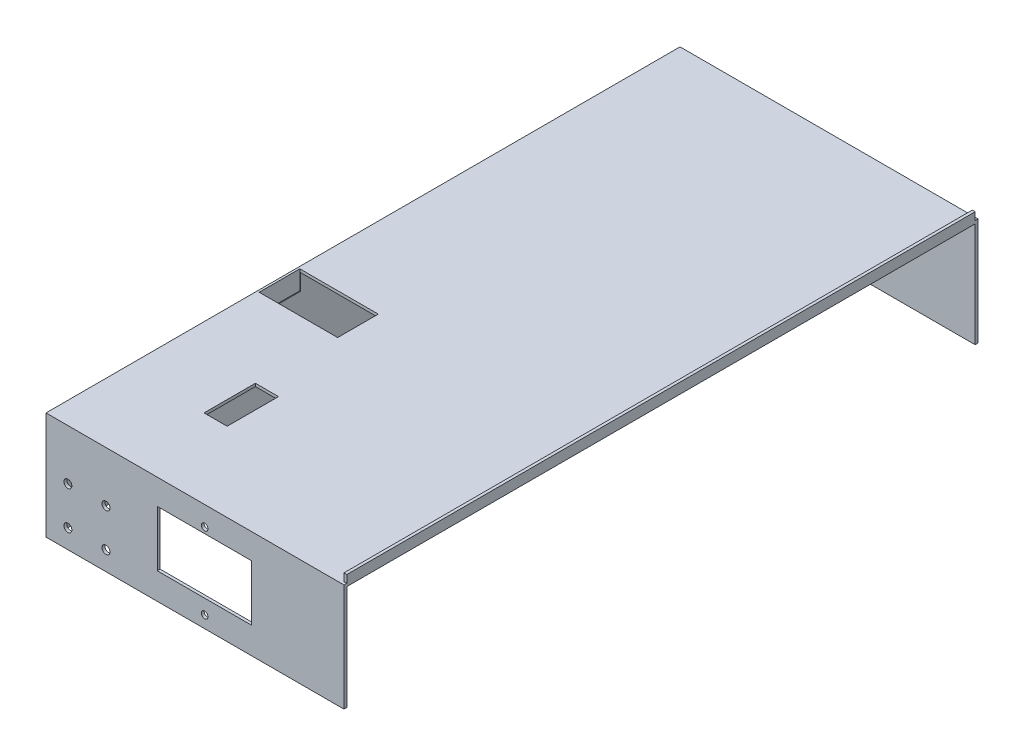
SolidWorks part; units mm, degrees
ref_plane "Front Plane" through (0, 0, 0) normal (0, 0, 1) x (1, 0, 0)
ref_plane "Top Plane" through (0, 0, 0) normal (0, 1, 0) x (1, 0, 0)
ref_plane "Right Plane" through (0, 0, 0) normal (1, 0, 0) x (0, 0, -1)
sketch "Sketch4" plane through (0, 0, 0) normal (0, 1, 0) x (1, 0, 0)
  line L0 (189.3737, 330) -> (344.3737, 330)
  line L1 (344.3737, 330) -> (344.3737, 0)
  line L2 (344.3737, 0) -> (189.3737, 0)
  line L3 (189.3737, 0) -> (189.3737, 65)
  line L7 (189.3737, 130) -> (189.3737, 330)
  line L8 (189.3737, 130) -> (189.3737, 65)
  line L10 (229.3737, 40) -> (241.5168, 40)
  line L11 (229.3737, 40) -> (229.3737, 66.9752)
  line L12 (229.3737, 66.9752) -> (241.5168, 66.9752)
  line L13 (241.5168, 40) -> (241.5168, 66.9752)
  point P12 (243.8504, 57.2947)
  dimension "D2" = 200
  dimension "D5" = 155
  dimension "D6" = 155
extrude "Boss-Extrude4" add sketch "Sketch4" along normal blind 1.5 separate body
sketch "Sketch5" plane through (0, 0, 0) normal (0, 0, 1) x (1, 0, 0)
  line L1 (189.3737, 1.5) -> (344.3737, 1.5)
  line L2 (189.3737, 1.5) -> (189.3737, -55)
  line L3 (189.3737, -55) -> (344.3737, -55)
  line L4 (344.3737, 1.5) -> (344.3737, -55)
  dimension "D1" = 56.5
sketch "Sketch7" plane through (0, 0, -330) normal (0, 0, -1) x (-1, 0, 0)
  line L1 (-189.3737, 1.5) -> (-344.3737, 1.5)
  line L2 (-189.3737, 1.5) -> (-189.3737, -55)
  line L3 (-189.3737, -55) -> (-344.3737, -55)
  line L4 (-344.3737, 1.5) -> (-344.3737, -55)
  point P5 (0, 0)
  point P6 (-189.3737, -52.5)
  point P7 (0, 0)
  dimension "D1" = 56.5
sketch "Sketch8" plane through (0, 1.5, 0) normal (0, 1, 0) x (1, 0, 0)
  line L0 (189.3737, 330) -> (344.3737, 330) construction
  line L1 (344.3737, 0) -> (342.8737, 0)
  line L2 (344.3737, 0) -> (344.3737, 330)
  line L3 (344.3737, 330) -> (342.8737, 330)
  line L4 (342.8737, 0) -> (342.8737, 330)
  dimension "D1" = 1.5
extrude "Boss-Extrude5" add sketch "Sketch5" along normal blind 1.5
extrude "Boss-Extrude14" add sketch "Sketch8" along normal blind 4
extrude "Boss-Extrude18" add sketch "Sketch7" along normal blind 1.5
sketch "Sketch9" plane through (189.3737, 0, 0) normal (-1, 0, 0) x (0, 0, 1)
  line L1 (-331.5, 1.5) -> (1.5, 1.5)
  line L2 (-331.5, 1.5) -> (-331.5, -55)
  line L3 (-331.5, -55) -> (1.5, -55)
  line L4 (1.5, 1.5) -> (1.5, -55)
extrude "Boss-Extrude19" add sketch "Sketch9" along normal blind 1.5
sketch "Sketch10" plane through (0, 0, 1.5) normal (0, 0, 1) x (1, 0, 0)
  circle A0 centre (219.3737, -45) radius 2.1
sketch "Sketch11" plane through (0, 0, 1.5) normal (0, 0, 1) x (1, 0, 0)
  circle A0 centre (199.3737, -45) radius 2.1
sketch "Sketch12" plane through (0, 0, 1.5) normal (0, 0, 1) x (1, 0, 0)
  circle A0 centre (199.3737, -25) radius 2.1
sketch "Sketch14" plane through (0, 0, 1.5) normal (0, 0, 1) x (1, 0, 0)
  circle A0 centre (219.3737, -25) radius 2.1
sketch "Sketch15" plane through (0, 0, -331.5) normal (0, 0, -1) x (-1, 0, 0)
  circle A0 centre (-219.3737, -25) radius 2.1
  circle A1 centre (-199.3737, -25) radius 2.1
  circle A2 centre (-219.3737, -45) radius 2.1
  circle A3 centre (-199.3737, -45) radius 2.1
extrude "Cut-Extrude1" cut sketch "Sketch15" against normal blind 10
extrude "Cut-Extrude2" cut sketch "Sketch14" against normal blind 10
extrude "Cut-Extrude3" cut sketch "Sketch12" against normal blind 10
extrude "Cut-Extrude4" cut sketch "Sketch10" against normal blind 10
extrude "Cut-Extrude5" cut sketch "Sketch11" against normal blind 10
sketch "Sketch17" plane through (0, 1.5, 0) normal (0, 1, 0) x (1, 0, 0)
  line L1 (188.9783, 130.6876) -> (230.1918, 130.6876)
  line L2 (188.9783, 130.6876) -> (188.9783, 109.3583)
  line L3 (188.9783, 109.3583) -> (230.1918, 109.3583)
  line L4 (230.1918, 130.6876) -> (230.1918, 109.3583)
  point P4 (188.9783, 130.6876)
  point P6 (189.3737, 131.1152)
extrude "Cut-Extrude6" cut sketch "Sketch17" against normal blind 10
sketch "Sketch18" plane through (0, 0, 1.5) normal (0, 0, 1) x (1, 0, 0)
  line L1 (246.3048, -11.7715) -> (295.8862, -11.7715)
  line L2 (246.3048, -11.7715) -> (246.3048, -41.091)
  line L3 (246.3048, -41.091) -> (295.8862, -41.091)
  line L4 (295.8862, -11.7715) -> (295.8862, -41.091)
  point P4 (246.3048, -11.7715)
  point P5 (0, 0)
  point P6 (295.8862, -41.091)
  point P8 (0, 0)
  point P9 (0, 0)
sketch "Sketch19" plane through (0, 0, 1.5) normal (0, 0, 1) x (1, 0, 0)
  circle A0 centre (271.1965, -8.7391) radius 1.75
  circle A1 centre (271.1965, -48.7391) radius 1.75
extrude "Cut-Extrude7" cut sketch "Sketch18" against normal blind 10
extrude "Cut-Extrude8" cut sketch "Sketch19" against normal blind 10
